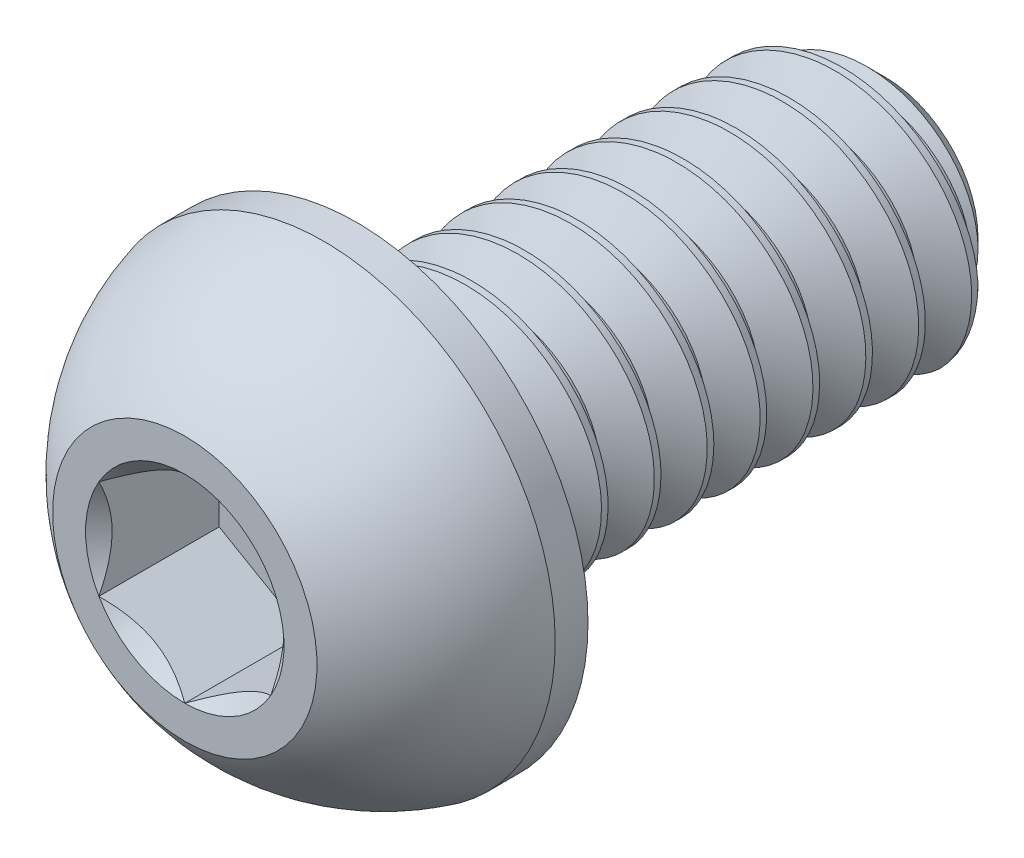
SolidWorks part; units mm, degrees
ref_plane "Front" through (0, 0, 0) normal (0, 0, 1) x (1, 0, 0)
ref_plane "Top" through (0, 0, 0) normal (0, 1, 0) x (1, 0, 0)
ref_plane "Right" through (0, 0, 0) normal (1, 0, 0) x (0, 0, -1)
ref_plane "Base of Head Plane" through (0, 0, -1.3) normal (0, 0, -1) x (-1, 0, 0)
sketch "Shaft Sketch" plane through (0, 0, -1.3) normal (0, 0, -1) x (-1, 0, 0)
  circle A0 centre (0, 0) radius 1
  dimension "D1" = 2
extrude "Shaft Extrude" add sketch "Shaft Sketch" along normal blind 4
sketch "Sketch3" plane through (0, 0, -5.3) normal (0, 0, -1) x (-1, 0, 0)
  circle A0 centre (0, 0) radius 1
  dimension "D1" = 2
curve "Thread Helix/Spiral" pitch 0.4 height 4.8 turns 12 parameters "Spiral Length"=4.8
sketch "Sketch2" plane through (0, 0, 0) normal (1, 0, 0) x (0, 0, -1)
  line L0 (5.3, 1) -> (5.65, 1)
  line L1 (5.65, 1) -> (5.5, 0.7402)
  line L2 (5.5, 0.7402) -> (5.45, 0.7402)
  line L3 (5.45, 0.7402) -> (5.3, 1)
  line L4 (5.375, 0.8701) -> (5.575, 0.8701) construction
  line L5 (5.3, -1) -> (5.3, 1) construction
  line L6 (0, 0) -> (38.9292, 0) construction
  dimension "D1" = 60
  dimension "D4" = 1
chamfer "Tip Chamfer" distance 0.3 angle 45 1 edges at (-1, 0, -5.3)
sweep "Thread Cut Sweep" cut profiles "Sketch2" path "Thread Helix/Spiral"
sketch "Head Sketch" plane through (0, 0, 0) normal (1, 0, 0) x (0, 0, -1)
  line L12 (1.052, 1.75) -> (1.3, 1.75)
  line L13 (0, 0) -> (1.3, 0)
  line L15 (1.3, 1.75) -> (1.3, 0)
  line L16 (0, 1) -> (0, 0)
  arc A3 (1.052, 1.75) -> (0, 1) centre (1.5063, 0) ccw
  dimension "Head Radius" = 1.75
  dimension "D2" = 1.3
  dimension "D3" = 0.248
revolve "Head Revolve" add sketch "Head Sketch" angle 360 mid plane about L13
sketch "Sketch5" plane through (0, 0, 0) normal (0, 0, 1) x (1, 0, 0)
  line L1 (0.65, -0.3753) -> (0.65, 0.3753)
  line L2 (0.65, 0.3753) -> (0, 0.7506)
  line L3 (0, 0.7506) -> (-0.65, 0.3753)
  line L4 (-0.65, 0.3753) -> (-0.65, -0.3753)
  line L5 (-0.65, -0.3753) -> (0, -0.7506)
  line L6 (0, -0.7506) -> (0.65, -0.3753)
  circle A0 centre (0, 0) radius 0.65 construction
  dimension "D1" = 1.3
extrude "Hex Cut Extrude" cut sketch "Sketch5" against normal blind 0.91
sketch "Sketch6" plane through (0, 0, 0) normal (0, 0, 1) x (1, 0, 0)
  circle A0 centre (0, 0) radius 0.7506
extrude "Hex Entry Cut Extrude" cut sketch "Sketch6" against normal blind 0.91 draft 45
sketch "Partial Thread Sketch" plane through (0, 0, -1.3) normal (0, 0, 1) x (1, 0, 0)
  circle A2 centre (0, 0) radius 1
  dimension "D1" = 2
extrude "Partial Thread Extrude" [suppressed] add sketch "Partial Thread Sketch" against normal offset from surface (7 mm away) 18 separate body
chamfer "Partial Thread Chamfer" [suppressed] distance 0.1 angle 45
combine bodies "Partial Thread Combine" [suppressed] operation type add bodies to combine 118 113
equation "\"D2@Sketch2\" = \"Thread Pitch\" * .125"
equation "\"D3@Sketch2\" = \"Thread Pitch\" * .5"
equation "\"D1@Tip Chamfer\" = \"Thread Pitch\" * .75"
equation "\"D1@Hex Entry Cut Extrude\" = \"D1@Hex Cut Extrude\""
equation "\"Screw Diameter\"= 2.0mm"
equation "\"D1@Sketch3\"=\"Screw Diameter\""
equation "\"D1@Shaft Sketch\"=\"Screw Diameter\""
equation "\"Thread Pitch\"= 0.4mm"
equation "\"D4@Thread Helix/Spiral\" = \"Thread Pitch\""
equation "\"Head Height\"= 1.3mm"
equation "\"D2@Head Sketch\"=\"Head Height\""
equation "\"D1@Base of Head Plane\"=\"Head Height\""
equation "\"D1@Head Sketch\"=\"Screw Diameter\"/2"
equation "\"Hex Size\"= 1.3mm"
equation "\"D1@Sketch5\"=\"Hex Size\""
equation "\"D1@Hex Cut Extrude\"=\"Head Height\"*.7"
equation "\"D1@Partial Thread Sketch\" = \"Screw Diameter\""
equation "\"Head Diameter\"= 3.5mm"
equation "\"Head Radius@Head Sketch\"=0.5*\"Head Diameter\""
equation "\"Spiral Length@Thread Helix/Spiral\"=(2+round(\"Screw Length\" / \"Thread Pitch\"))*\"Thread Pitch\""
equation "\"D4@Sketch2\"=\"Screw Diameter\"/2"
